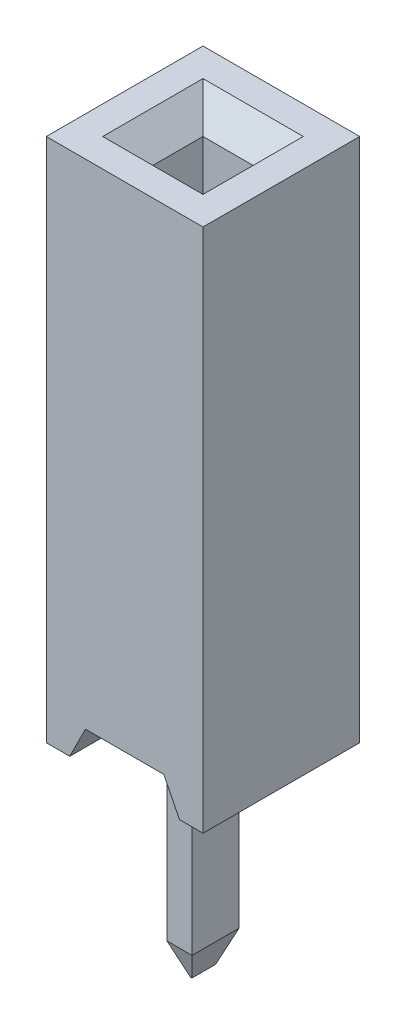
SolidWorks part; units mm, degrees
ref_plane "Front Plane" through (0, 0, 0) normal (0, 0, 1) x (1, 0, 0)
ref_plane "Top Plane" through (0, 0, 0) normal (0, 1, 0) x (1, 0, 0)
ref_plane "Right Plane" through (0, 0, 0) normal (1, 0, 0) x (0, 0, -1)
sketch "Sketch1" plane through (0, 0, 0) normal (0, 1, 0) x (1, 0, 0)
  line L1 (0, 0) -> (2.54, 0)
  line L2 (0, 0) -> (0, 2.54)
  line L3 (0, 2.54) -> (2.54, 2.54)
  line L4 (2.54, 0) -> (2.54, 2.54)
  dimension "D1" = 2.54
  dimension "D2" = 2.54
extrude "Boss-Extrude1" add sketch "Sketch1" along normal blind 8.509
sketch "Sketch2" plane through (0, 8.509, 0) normal (0, 1, 0) x (1, 0, 0)
  line L0 (0, 2.54) -> (0, 0) construction
  line L1 (0, 0) -> (2.54, 0) construction
  line L2 (1.27, 0) -> (1.27, 2.0363) construction
  line L3 (1.6764, 1.6764) -> (0.8636, 1.6764)
  line L4 (1.6764, 1.6764) -> (1.6764, 0.8636)
  line L5 (1.6764, 0.8636) -> (0.8636, 0.8636)
  line L6 (0.8636, 1.6764) -> (0.8636, 0.8636)
  line L7 (1.6764, 1.6764) -> (0.8636, 0.8636) construction
  line L8 (1.6764, 0.8636) -> (0.8636, 1.6764) construction
  line L9 (0, 1.27) -> (2.1183, 1.27) construction
  point P0 (0, 1.27)
  point P1 (1.27, 0)
  point P4 (1.27, 1.27)
  point P7 (1.27, 1.27)
  dimension "D1" = 0.8128
  dimension "D2" = 0.8128
  dimension "D3" = 0
  dimension "D4" = 0
sketch "Sketch4" plane through (0, 0, -2.54) normal (0, 0, -1) x (-1, 0, 0)
  line L0 (-2.54, 0) -> (0, 0) construction
  line L1 (-1.905, 0) -> (-0.635, 0)
  line L2 (-1.905, 0) -> (-1.905, 0.508)
  line L3 (-1.905, 0.508) -> (-0.635, 0.508)
  line L4 (-0.635, 0) -> (-0.635, 0.508)
  line L5 (-1.905, 0.508) -> (-2.159, 0)
  line L6 (-2.159, 0) -> (-0.381, 0)
  line L7 (-0.381, 0) -> (-0.635, 0.508)
  line L8 (-2.54, 0.5762) -> (0, 0.5762) construction
  line L9 (-2.54, 8.509) -> (-2.54, 0) construction
  line L10 (0, 8.509) -> (0, 0) construction
  point P6 (-1.27, 0)
  point P15 (-1.27, 0.5762)
  point P16 (-1.27, 0.508)
  line M5 (-2.54, 0) -> (0, 0)
  dimension "D1" = 1.27
  dimension "D2" = 0.254
  dimension "D3" = 0.254
  dimension "D4" = 0.508
extrude "Cut-Extrude1" cut sketch "Sketch4" against normal blind 2.54 contours L2 L5 M5 | L4 L3 L2 M5 | L7 L4 M5 region at (1.27, 0.254, -2.54) region at (1.9897, 0.1693, -2.54) region at (0.5503, 0.1693, -2.54)
sketch "Sketch3" plane through (0, 0.508, 0) normal (0, -1, 0) x (1, 0, 0)
  line L0 (1.905, -2.54) -> (0.635, -2.54) construction
  line L1 (0.635, 0) -> (0.635, -2.54) construction
  line L8 (1.0668, -0.889) -> (1.0668, -1.651)
  line L9 (1.4732, -0.889) -> (1.0668, -0.889)
  line L10 (1.4732, -1.651) -> (1.4732, -0.889)
  line L11 (1.0668, -1.651) -> (1.4732, -1.651)
  point P2 (1.27, -2.54)
  point P5 (0.635, -1.27)
  point P8 (1.0668, -1.27)
  point P11 (1.27, -1.651)
  dimension "D1" = 0.4064
  dimension "D2" = 0.762
extrude "Boss-Extrude3" add sketch "Sketch3" along normal blind 3.7084
chamfer "Chamfer2" distance 0.508 distance2 0.1905 4 edges at (1.4732, -3.2004, -1.27) (1.27, -3.2004, -1.651) (1.0668, -3.2004, -1.27) (1.27, -3.2004, -0.889) first distance on face at (1.4732, -1.3462, -1.27) first distance on face at (1.27, -1.3462, -1.651) first distance on face at (1.0668, -1.3462, -1.27) first distance on face at (1.27, -1.3462, -0.889)
extrude "Cut-Extrude2" cut sketch "Sketch2" against normal blind 6.35 contours L6 L5 L4 L3
chamfer "Chamfer3" distance 0.4064 angle 45 4 edges at (1.27, 8.509, -1.6764) (0.8636, 8.509, -1.27) (1.27, 8.509, -0.8636) (1.6764, 8.509, -1.27)
